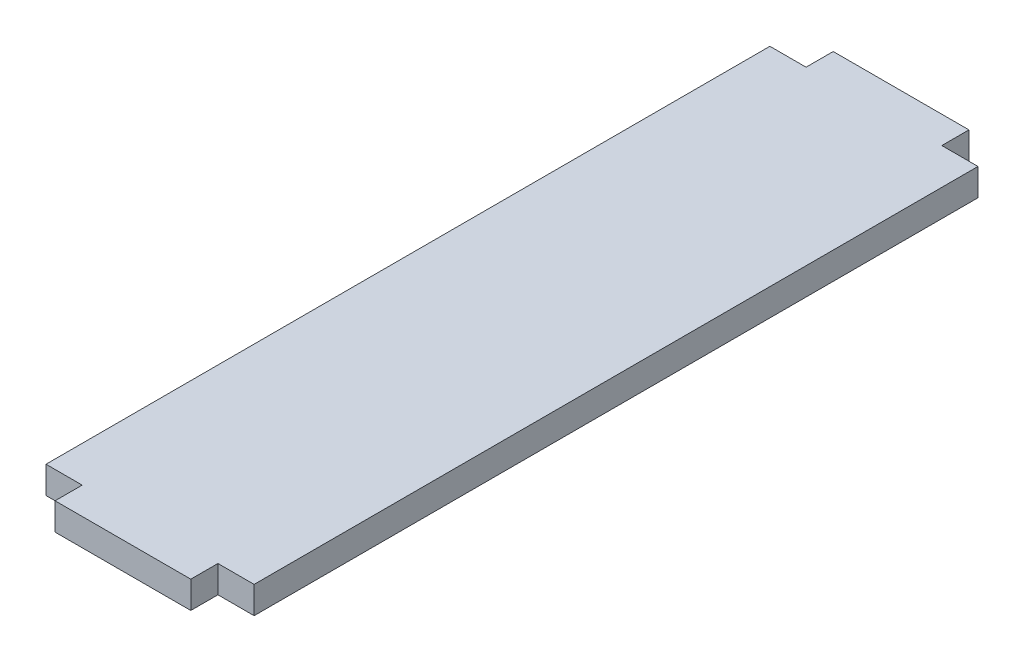
SolidWorks part; units mm, degrees
material "AISI 304"
ref_plane "Front Plane" through (0, 0, 0) normal (0, 0, 1) x (1, 0, 0)
ref_plane "Top Plane" through (0, 0, 0) normal (0, 1, 0) x (1, 0, 0)
ref_plane "Right Plane" through (0, 0, 0) normal (1, 0, 0) x (0, 0, -1)
sketch "Sketch1" plane through (0, 0, 0) normal (0, 1, 0) x (1, 0, 0)
  line L0 (3.75, 20) -> (5.75, 20)
  line L1 (-5.75, -20) -> (-3.75, -20)
  line L2 (-5.75, -20) -> (-5.75, 20)
  line L3 (-5.75, 20) -> (-3.75, 20)
  line L4 (5.75, -20) -> (5.75, 20)
  line L5 (-5.75, -20) -> (5.75, 20) construction
  line L6 (-5.75, 20) -> (5.75, -20) construction
  line L8 (-3.75, 20) -> (-3.75, 21.5)
  line L9 (-3.75, 21.5) -> (3.75, 21.5)
  line L10 (3.75, 20) -> (3.75, 21.5)
  line L12 (-3.75, -20) -> (-3.75, -21.5)
  line L13 (-3.75, -21.5) -> (3.75, -21.5)
  line L14 (3.75, -20) -> (3.75, -21.5)
  line L15 (3.75, -20) -> (5.75, -20)
  point P0 (0, 0)
  dimension "D1" = 2
  dimension "D2" = 2
  dimension "D3" = 7.5
  dimension "D4" = 2
  dimension "D5" = 2
  dimension "D6" = 1.5
  dimension "D7" = 1.5
  dimension "D8" = 40
extrude "Boss-Extrude1" add sketch "Sketch1" along normal blind 1.5
